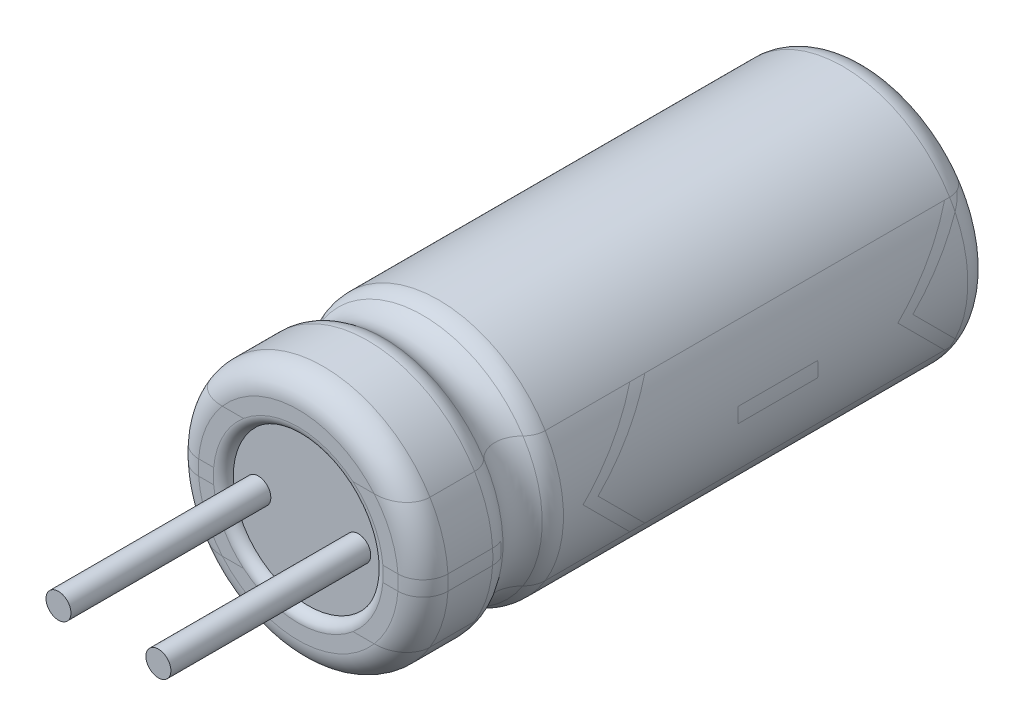
SolidWorks part; units mm, degrees
ref_plane "Спереди" through (0, 0, 0) normal (0, 0, 1) x (1, 0, 0)
ref_plane "Сверху" through (0, 0, 0) normal (0, 1, 0) x (1, 0, 0)
ref_plane "Справа" through (0, 0, 0) normal (1, 0, 0) x (0, 0, -1)
sketch "Эскиз1" plane through (0, 0, 0) normal (1, 0, 0) x (0, 0, -1)
  line L0 (-10.8114, 0) -> (11.7084, 0) construction
  line L1 (-5.7, 0) -> (-5.7, 2.5)
  line L2 (-5.7, 2.5) -> (-4.3071, 2.5)
  line L3 (-2.8929, 2.5) -> (5.7, 2.5)
  line L4 (5.7, 2.5) -> (5.7, 0)
  line L5 (5.7, 0) -> (-5.7, 0)
  arc A1 (-3.9928, 2.3889) -> (-3.2072, 2.3889) centre (-3.6, 2.875) ccw
  arc A2 (-2.8929, 2.5) -> (-3.2072, 2.3889) centre (-2.8929, 2) ccw
  arc A3 (-4.3071, 2.5) -> (-3.9928, 2.3889) centre (-4.3071, 2) cw
  point P5 (-3.6, 2.25)
  point P11 (0, 0)
  point P14 (-3.1, 2.5)
  point P17 (-4.1, 2.5)
  dimension "D6" = 0.5
  dimension "D1" = 11.4
  dimension "D2" = 1.6
  dimension "D3" = 2.5
  dimension "D4" = 1
  dimension "D5" = 2.25
revolve "Повернуть1" add sketch "Эскиз1" angle 360 about L0
sketch "Эскиз2" plane through (0, 0, 5.7) normal (0, 0, 1) x (1, 0, 0)
  circle A0 centre (0, 0) radius 1.5
  dimension "D1" = 3
extrude "Вырез-Вытянуть1" cut sketch "Эскиз2" against normal blind 0.2
sketch "Эскиз3" plane through (0, 0, 5.5) normal (0, 0, 1) x (1, 0, 0)
  line L0 (0, 2.6593) -> (0, -2.1879) construction
  circle A0 centre (-1, 0) radius 0.25
  circle A1 centre (1, 0) radius 0.25
  dimension "D1" = 0.5
  dimension "D2" = 1
extrude "Бобышка-Вытянуть1" add sketch "Эскиз3" along normal blind 4 separate body
sketch "Эскиз4" plane through (0, 0, -5.7) normal (0, 0, -1) x (-1, 0, 0)
  circle A0 centre (0, 0) radius 1.5
  dimension "D1" = 3
extrude "Вырез-Вытянуть2" cut sketch "Эскиз4" against normal blind 0.3
fillet "Скругление1" radius 0.5 2 edges at (2.5, 0, -5.7) (2.5, 0, 5.7)
fillet "Скругление2" radius 0.2 2 edges at (-1.5, 0, -5.7) (1.5, 0, 5.7)
ref_plane "Плоскость2" through (-2.7, 0, 0) normal (1, 0, 0) x (0, 0, -1)
sketch "Эскиз5" plane through (-2.7, 0, 0) normal (1, 0, 0) x (0, 0, -1)
  line L0 (5.9441, 0) -> (-9.6465, 0) construction
  line L1 (5.4, 1.3) -> (4.1, 0)
  line L2 (6.1923, 1.3) -> (-6.2778, 1.3)
  line L3 (6.1923, 1.3) -> (6.1923, -1.3)
  line L4 (6.1923, -1.3) -> (-6.2778, -1.3)
  line L5 (-6.2778, 1.3) -> (-6.2778, -1.3)
  line L6 (4.1, 0) -> (5.4, -1.3)
  line L7 (5.1, 1.3) -> (3.8, 0)
  line L8 (3.8, 0) -> (5.1, -1.3)
  line L9 (5.1, -1.3) -> (5.4, -1.3)
  line L10 (5.4, 1.3) -> (5.1, 1.3)
  line L11 (5.7, -2) -> (5.7, 2) construction
  line L13 (2.2, 0.15) -> (0.6, 0.15)
  line L14 (2.2, 0.15) -> (2.2, -0.15)
  line L15 (2.2, -0.15) -> (0.6, -0.15)
  line L16 (0.6, 0.15) -> (0.6, -0.15)
  line L17 (2.2, 0.15) -> (0.6, -0.15) construction
  line L18 (2.2, -0.15) -> (0.6, 0.15) construction
  line L24 (-0.9, 1.3) -> (-2.2, 0)
  line L25 (-2.2, 0) -> (-0.9, -1.3)
  line L26 (-1.2, 1.3) -> (-2.5, 0)
  line L27 (-2.5, 0) -> (-1.2, -1.3)
  line L28 (-1.2, -1.3) -> (-0.9, -1.3)
  line L29 (-0.9, 1.3) -> (-1.2, 1.3)
  line L30 (-4.3071, 2.5) -> (-4.3071, -2.5) construction
  line L31 (-4.1, 0.15) -> (-5.7, 0.15)
  line L32 (-4.1, 0.15) -> (-4.1, -0.15)
  line L33 (-4.1, -0.15) -> (-5.7, -0.15)
  line L34 (-5.7, 0.15) -> (-5.7, -0.15)
  line L35 (-4.1, 0.15) -> (-5.7, -0.15) construction
  line L36 (-4.1, -0.15) -> (-5.7, 0.15) construction
  point P15 (1.4, 0)
  point P30 (-4.9, 0)
  dimension "D1" = 2.6
  dimension "D2" = 1.3
  dimension "D3" = 0.3
  dimension "D4" = 0.3
  dimension "D5" = 0.3
  dimension "D6" = 0.3
  dimension "D7" = 0.3
  dimension "D8" = 1.6
  dimension "D9" = 0.3
  dimension "D10" = 1.6
  dimension "D11" = 1.6
  dimension "D12" = 0.3
  dimension "D13" = 0.3
  dimension "D14" = 0.3
  dimension "D15" = 1.6
  dimension "D16" = 1.6
  dimension "D17" = 2.6
  dimension "D18" = 2.8
  dimension "D19" = 1.6
  dimension "D20" = 1.8071
  dimension "D21" = 1.6
  dimension "D22" = 0.3
split line "Разделяющая линия1"
